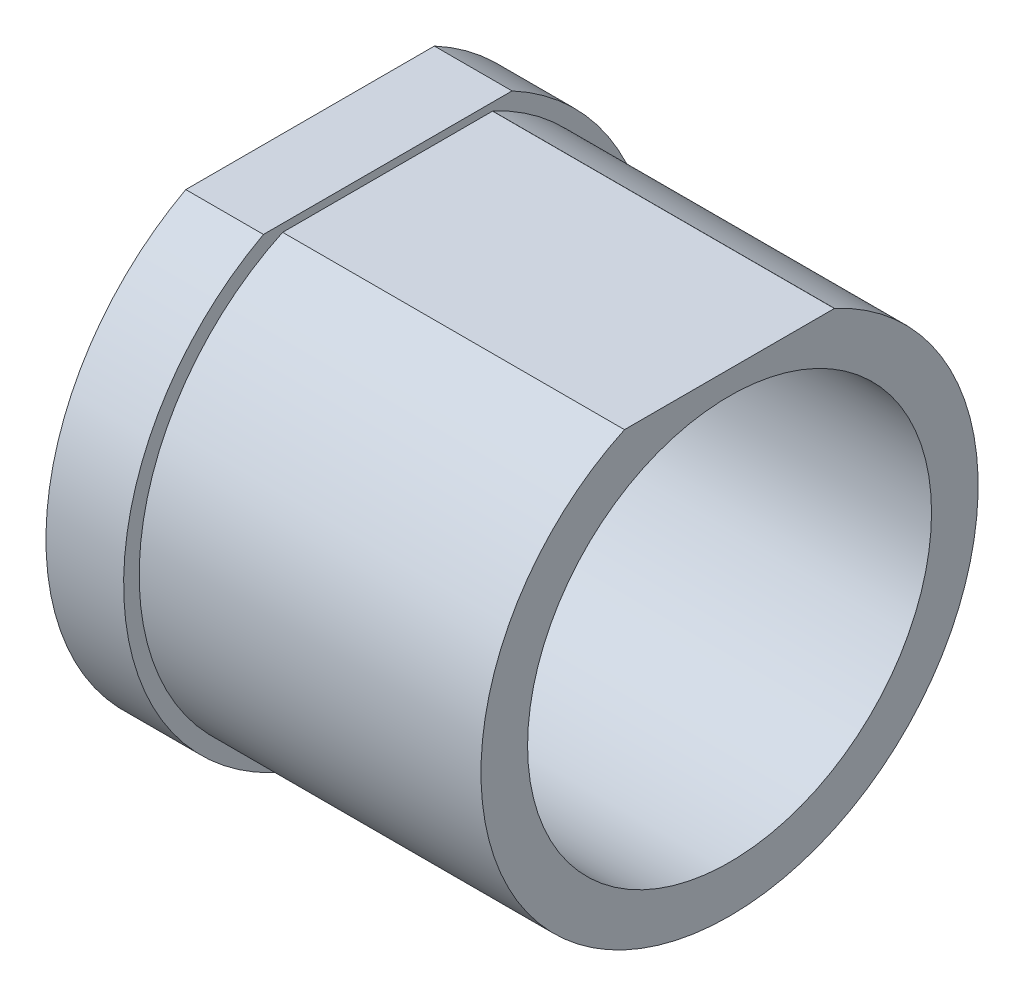
SolidWorks part; units mm, degrees
ref_plane "Front Plane" through (0, 0, 0) normal (0, 0, 1) x (1, 0, 0)
ref_plane "Top Plane" through (0, 0, 0) normal (0, 1, 0) x (1, 0, 0)
ref_plane "Right Plane" through (0, 0, 0) normal (1, 0, 0) x (0, 0, -1)
sketch "Sketch1" plane through (0, 0, 0) normal (1, 0, 0) x (0, 0, -1)
  circle A0 centre (0, 0) radius 34
extrude "Boss-Extrude1" add sketch "Sketch1" along normal blind 10
sketch "Sketch2" plane through (10, 0, 0) normal (1, 0, 0) x (0, 0, -1)
  circle A0 centre (0, 0) radius 32
extrude "Boss-Extrude2" add sketch "Sketch2" along normal blind 44
sketch "Sketch3" plane through (54, 0, 0) normal (1, 0, 0) x (0, 0, -1)
  circle A0 centre (0, 0) radius 26
extrude "Cut-Extrude1" cut sketch "Sketch3" against normal through all
sketch "Sketch4" plane through (54, 0, 0) normal (1, 0, 0) x (0, 0, -1)
  line L1 (-13.5619, 36.688) -> (13.4918, 36.688)
  line L2 (-13.5619, 36.688) -> (-13.5619, 29)
  line L3 (-13.5619, 29) -> (13.4918, 29)
  line L4 (13.4918, 36.688) -> (13.4918, 29)
  circle A0 centre (0, 0) radius 32 construction
  circle A1 centre (0, 0) radius 26 construction
  dimension "D1" = 6
  dimension "D2" = 29
  dimension "D3" = 7.688
  dimension "D4" = 27.0537
  dimension "D5" = 13.5619
extrude "Cut-Extrude2" cut sketch "Sketch4" against normal blind 44
sketch "Sketch5" plane through (0, 0, 0) normal (-1, 0, 0) x (0, 0, 1)
  line L1 (-23.6606, 37.2904) -> (25.7815, 37.2904)
  line L2 (-23.6606, 37.2904) -> (-23.6606, 30)
  line L3 (-23.6606, 30) -> (25.7815, 30)
  line L4 (25.7815, 37.2904) -> (25.7815, 30)
  circle A0 centre (0, 0) radius 34 construction
  circle A1 centre (0, 0) radius 26 construction
  dimension "D1" = 8
  dimension "D2" = 30
  dimension "D3" = 7.2904
  dimension "D4" = 49.4421
  dimension "D5" = 23.6606
extrude "Cut-Extrude3" cut sketch "Sketch5" against normal up to next
equation "\"D2@Sketch4\"=26+\"D1@Sketch4\"/2"
equation "\"D2@Sketch5\"=26+\"D1@Sketch5\"/2"
